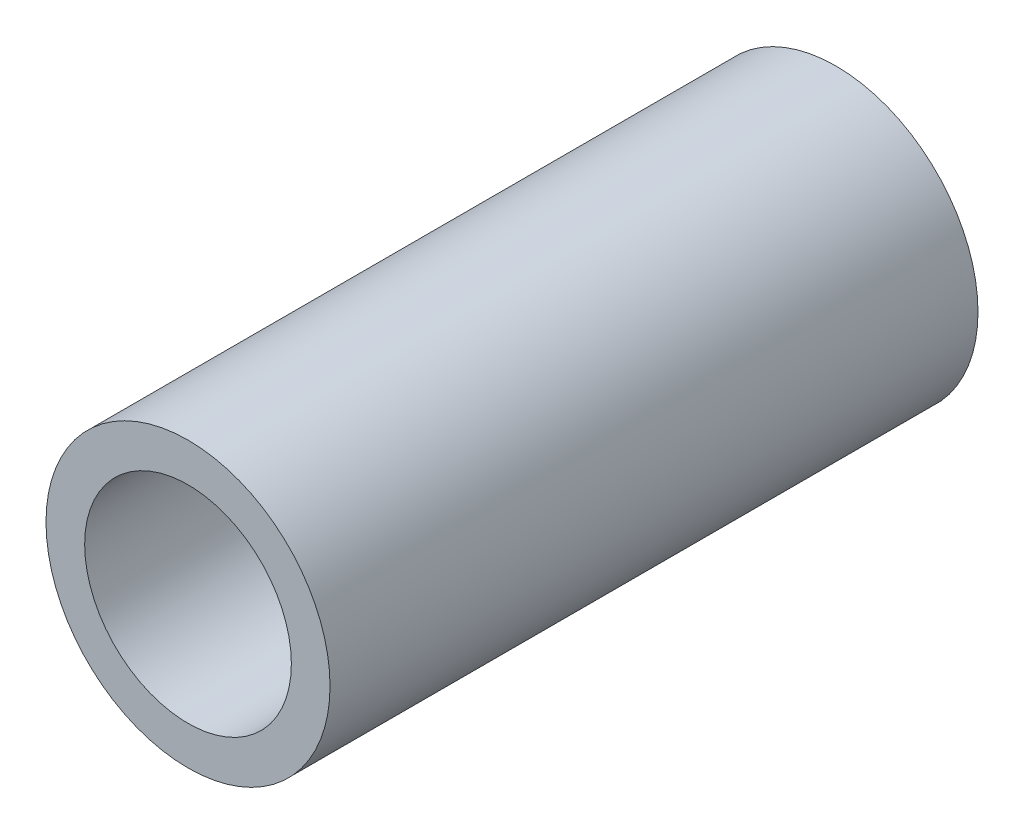
SolidWorks part; units mm, degrees
ref_plane "Front Plane" through (0, 0, 0) normal (0, 0, 1) x (1, 0, 0)
ref_plane "Top Plane" through (0, 0, 0) normal (0, 1, 0) x (1, 0, 0)
ref_plane "Right Plane" through (0, 0, 0) normal (1, 0, 0) x (0, 0, -1)
sketch "Sketch1" plane through (0, 0, 0) normal (0, 0, 1) x (1, 0, 0)
  circle A0 centre (0, 0) radius 16.7005
  dimension "Pipe OD" = 33.401
extrude "Extrude-Thin1" add sketch "Sketch1" along normal blind 76.2 thin thin type one direction reverse wall 4.5466
